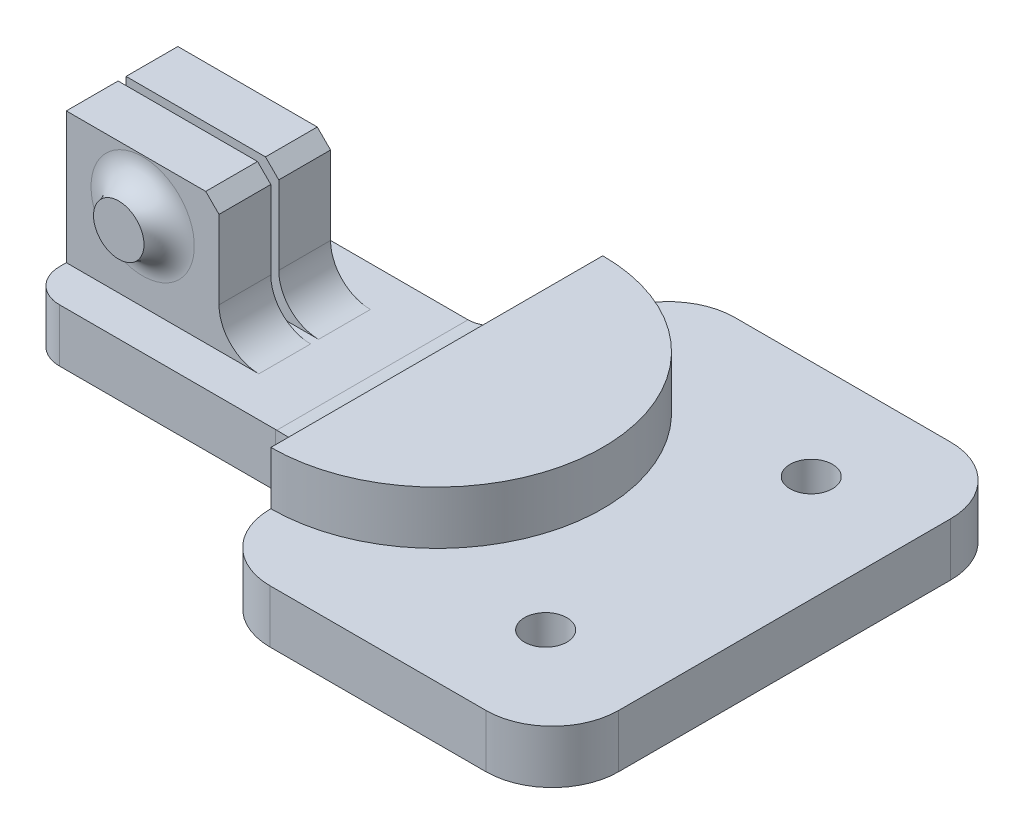
SolidWorks part; units mm, degrees
ref_plane "Alzado" through (0, 0, 0) normal (0, 0, 1) x (1, 0, 0)
ref_plane "Planta" through (0, 0, 0) normal (0, 1, 0) x (1, 0, 0)
ref_plane "Vista lateral" through (0, 0, 0) normal (1, 0, 0) x (0, 0, -1)
sketch "Croquis1" plane through (0, 0, 0) normal (0, 1, 0) x (1, 0, 0)
  line L1 (0, 0) -> (50, 0)
  line L2 (0, 0) -> (0, 35)
  line L3 (0, 35) -> (50, 35)
  line L4 (50, 0) -> (50, 35)
  circle A0 centre (42, 27.5) radius 1.6
  circle A1 centre (42, 7.5) radius 1.6
  point P9 (0, 0)
  point P10 (0, 0)
  dimension "D2" = 3.2
  dimension "D3" = 20
  dimension "D1" = 35
  dimension "D4" = 7.5
  dimension "D5" = 8
  dimension "D6" = 50
extrude "Saliente-Extruir1" add sketch "Croquis1" along normal blind 3
sketch "Croquis3" plane through (0, 3, 0) normal (0, 1, 0) x (1, 0, 0)
  line L0 (0, 35) -> (0, 0) construction
  line L1 (0, 17.3) -> (11.5, 17.3)
  line L2 (0, 17.3) -> (0, 13.4)
  line L3 (0, 13.4) -> (11.5, 13.4)
  line L4 (11.5, 17.3) -> (11.5, 13.4)
  line L5 (50, 35) -> (0, 35) construction
  line L6 (0, 21.8) -> (11.5, 21.8)
  line L7 (0, 21.8) -> (0, 17.9)
  line L8 (0, 17.9) -> (11.5, 17.9)
  line L9 (11.5, 21.8) -> (11.5, 17.9)
  dimension "D1" = 11.5
  dimension "D2" = 11.5
  dimension "D3" = 3.9
  dimension "D4" = 3.9
  dimension "D5" = 0.6
  dimension "D6" = 13.2
extrude "Saliente-Extruir2" add sketch "Croquis3" along normal blind 9.9
sketch "Croquis4" plane through (0, 0, -13.4) normal (0, 0, 1) x (1, 0, 0)
  line L0 (11.5, 12.9) -> (11.5, 3) construction
  line L1 (0, 3) -> (11.5, 3) construction
  circle A0 centre (5.75, 8.9) radius 1.9
  dimension "D3" = 3.8
  dimension "D1" = 5.75
  dimension "D2" = 5.9
extrude "Saliente-Extruir3" add sketch "Croquis4" along normal blind 1.8
sketch "Croquis5" plane through (0, 0, -21.8) normal (0, 0, -1) x (-1, 0, 0)
  circle A0 centre (-5.75, 8.9) radius 1.9 construction
  circle A1 centre (-5.75, 8.9) radius 1.9
extrude "Saliente-Extruir4" add sketch "Croquis5" along normal blind 1.8
fillet "Redondeo1" radius 2 2 edges at (7.65, 8.9, -21.8) (3.85, 8.9, -13.4)
fillet "Redondeo2" radius 3 2 edges at (11.5, 3, -19.85) (11.5, 3, -15.35)
sketch "Croquis6" plane through (0, 3, 0) normal (0, 1, 0) x (1, 0, 0)
  line L0 (50, 17.5) -> (0, 17.6) construction
  line L1 (50, 0) -> (50, 35) construction
  line L3 (23.75, 30.0525) -> (23.75, 5.0525)
  line L4 (0, 17.9) -> (0, 17.3) construction
  arc A0 (23.75, 5.0525) -> (23.75, 30.0525) centre (23.75, 17.5525) ccw
  point P7 (23.75, 17.5593)
  point P8 (23.75, 2.955)
  point P9 (23.75, 17.5525)
  dimension "D1" = 25
  dimension "D2" = 26.25
extrude "Saliente-Extruir5" add sketch "Croquis6" along normal blind 4
sketch "Croquis7" plane through (0, 3, 0) normal (0, 1, 0) x (1, 0, 0)
  line L0 (23.75, 30.0525) -> (23.75, 5.0525) construction
  line L1 (0, 35) -> (23.75, 35)
  line L2 (0, 35) -> (0, 24.8)
  line L3 (0, 24.8) -> (23.75, 24.8)
  line L4 (23.75, 35) -> (23.75, 24.8)
  line L5 (23.75, 30.0525) -> (23.75, 5.0525) construction
  line L6 (0, 0) -> (23.75, 0)
  line L7 (0, 0) -> (0, 10.4)
  line L8 (0, 10.4) -> (23.75, 10.4)
  line L9 (23.75, 0) -> (23.75, 10.4)
  line L10 (0, 13.4) -> (11.5, 13.4) construction
  line L11 (14.5, 21.8) -> (0, 21.8) construction
  dimension "D1" = 3
  dimension "D2" = 3
extrude "Cortar-Extruir1" cut sketch "Croquis7" against normal up to surface (3 mm away) up to face at (42, 0, -25.9)
chamfer "Chaflán1" distance 1 angle 45 2 edges at (11.5, 12.9, -15.35) (11.5, 12.9, -19.85)
fillet "Redondeo3" radius 5 7 edges at (23.75, 1.5, -24.8) (23.75, 1.5, -10.4) (23.75, 3, -17.6) (50, 1.5, -35) (50, 1.5, 0) (23.75, 1.5, -35) (23.75, 1.5, 0)
fillet "Redondeo4" radius 2.5 2 edges at (0, 1.5, -24.8) (0, 1.5, -10.4)
sketch "Croquis8" plane through (0, 0, 0) normal (0, -1, 0) x (1, 0, 0)
  line L8 (0, -12.9) -> (0, -22.3)
  line L9 (2.5, -24.8) -> (18.75, -24.8)
  line L10 (23.75, -29.8) -> (23.75, -30)
  line L11 (28.75, -35) -> (45, -35)
  line L12 (50, -30) -> (50, -5)
  line L13 (45, 0) -> (28.75, 0)
  line L14 (23.75, -5) -> (23.75, -5.4)
  line L15 (18.75, -10.4) -> (2.5, -10.4)
  line L16 (0, -12.9) -> (0, -22.3)
  line L17 (2.5, -24.8) -> (18.75, -24.8)
  line L18 (23.75, -29.8) -> (23.75, -30)
  line L19 (28.75, -35) -> (45, -35)
  line L20 (50, -30) -> (50, -5)
  line L21 (45, 0) -> (28.75, 0)
  line L22 (23.75, -5) -> (23.75, -5.4)
  line L23 (18.75, -10.4) -> (2.5, -10.4)
  circle A0 centre (42, -27.5) radius 1.6 construction
  circle A1 centre (42, -7.5) radius 1.6 construction
  circle A2 centre (42, -27.5) radius 1.6
  circle A3 centre (42, -7.5) radius 1.6
  arc A8 (0, -22.3) -> (2.5, -24.8) centre (2.5, -22.3) ccw
  arc A9 (23.75, -29.8) -> (18.75, -24.8) centre (18.75, -29.8) ccw
  arc A10 (23.75, -30) -> (28.75, -35) centre (28.75, -30) ccw
  arc A11 (45, -35) -> (50, -30) centre (45, -30) ccw
  arc A12 (50, -5) -> (45, 0) centre (45, -5) ccw
  arc A13 (28.75, 0) -> (23.75, -5) centre (28.75, -5) ccw
  arc A14 (18.75, -10.4) -> (23.75, -5.4) centre (18.75, -5.4) ccw
  arc A15 (2.5, -10.4) -> (0, -12.9) centre (2.5, -12.9) ccw
  arc A16 (0, -22.3) -> (2.5, -24.8) centre (2.5, -22.3) ccw
  arc A17 (23.75, -29.8) -> (18.75, -24.8) centre (18.75, -29.8) ccw
  arc A18 (23.75, -30) -> (28.75, -35) centre (28.75, -30) ccw
  arc A19 (45, -35) -> (50, -30) centre (45, -30) ccw
  arc A20 (50, -5) -> (45, 0) centre (45, -5) ccw
  arc A21 (28.75, 0) -> (23.75, -5) centre (28.75, -5) ccw
  arc A22 (18.75, -10.4) -> (23.75, -5.4) centre (18.75, -5.4) ccw
  arc A23 (2.5, -10.4) -> (0, -12.9) centre (2.5, -12.9) ccw
  dimension "D1" = 0
extrude "Saliente-Extruir6" add sketch "Croquis8" along normal blind 1
sketch "Croquis9" plane through (0, -1, 0) normal (0, -1, 0) x (1, 0, 0)
  line L0 (50, -30) -> (50, -5) construction
  line L1 (44.9, -5.8257) -> (42, -4.1514)
  line L2 (42, -4.1514) -> (39.1, -5.8257)
  line L3 (39.1, -5.8257) -> (39.1, -9.1743)
  line L4 (39.1, -9.1743) -> (42, -10.8486)
  line L5 (42, -10.8486) -> (44.9, -9.1743)
  line L6 (44.9, -9.1743) -> (44.9, -5.8257)
  line L7 (44.9, -25.8257) -> (42, -24.1514)
  line L8 (42, -24.1514) -> (39.1, -25.8257)
  line L9 (39.1, -25.8257) -> (39.1, -29.1743)
  line L10 (39.1, -29.1743) -> (42, -30.8486)
  line L11 (42, -30.8486) -> (44.9, -29.1743)
  line L12 (44.9, -29.1743) -> (44.9, -25.8257)
  circle A0 centre (42, -7.5) radius 2.9 construction
  circle A1 centre (42, -27.5) radius 2.9 construction
  dimension "D1" = 5.8
  dimension "D2" = 5.8
extrude "Cortar-Extruir2" cut sketch "Croquis9" against normal blind 0.5
